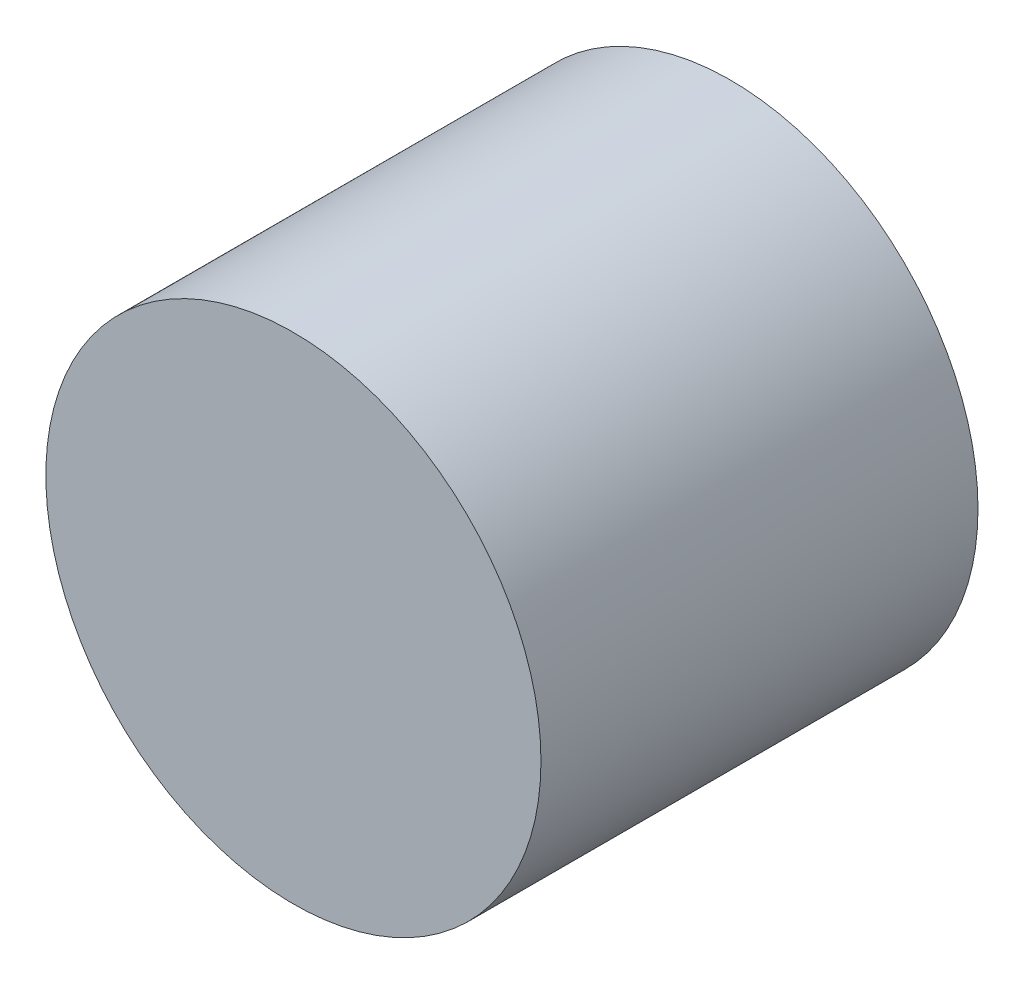
SolidWorks part; units mm, degrees
ref_plane "Front Plane" through (0, 0, 0) normal (1, 0, 0) x (0, 1, 0)
ref_plane "Top Plane" through (0, 0, 0) normal (0, 0, 1) x (0, 1, 0)
ref_plane "Right Plane" through (0, 0, 0) normal (0, 1, 0) x (-1, 0, 0)
sketch "Sketch1" plane through (0, 0, 0) normal (0, 0, 1) x (0, 1, 0)
  circle A0 centre (0, 0) radius 12.6619
  dimension "D1" = 25.3238
extrude "Boss-Extrude1" add sketch "Sketch1" along normal blind 22.352
